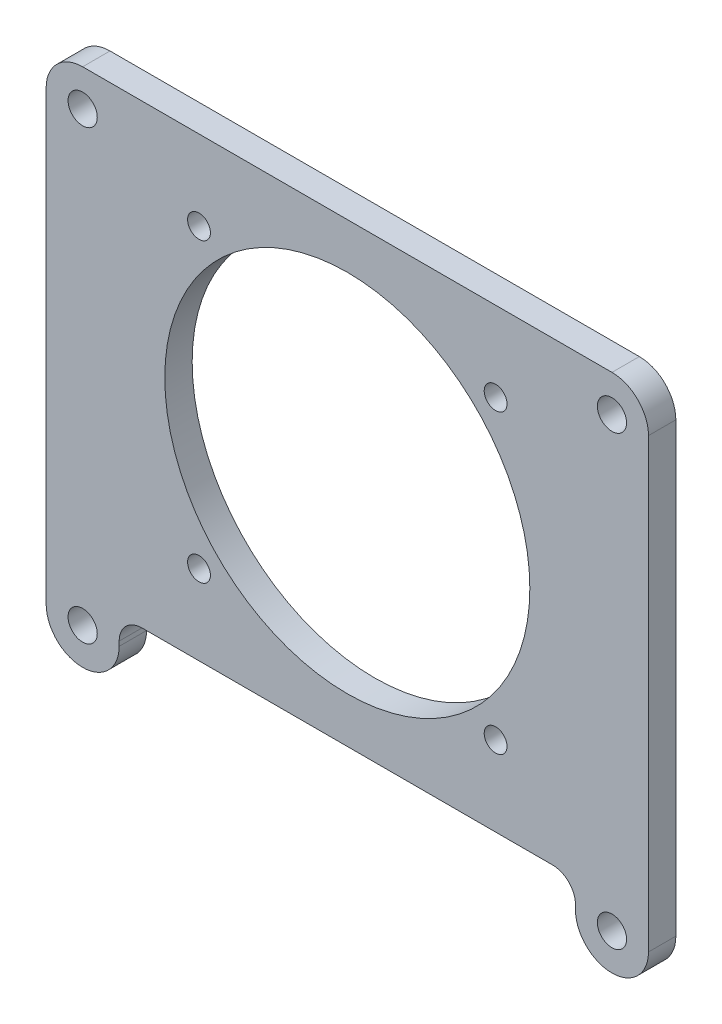
SolidWorks part; units mm, degrees
ref_plane "正面" through (0, 0, 0) normal (0, 0, 1) x (1, 0, 0)
ref_plane "平面" through (0, 0, 0) normal (0, 1, 0) x (1, 0, 0)
ref_plane "右側面" through (0, 0, 0) normal (1, 0, 0) x (0, 0, -1)
sketch "ｽｹｯﾁ1" plane through (0, 0, 0) normal (0, 0, 1) x (1, 0, 0)
  line L0 (22.5, 0) -> (-22.5, 0)
  line L1 (-25, -2.5) -> (-25, -3)
  line L2 (-33, -3) -> (-33, 46)
  line L3 (-29, 50) -> (29, 50)
  line L4 (0, 50) -> (0, 0) construction
  line L5 (-29, 46) -> (-29, -3) construction
  line L6 (33, -3) -> (33, 46)
  line L7 (25, -2.5) -> (25, -3)
  arc A0 (-33, -3) -> (-25, -3) centre (-29, -3) ccw
  arc A1 (-29, 50) -> (-33, 46) centre (-29, 46) ccw
  arc A2 (-25, -2.5) -> (-22.5, 0) centre (-22.5, -2.5) cw
  circle A3 centre (-29, -3) radius 1.6
  circle A4 centre (-29, 46) radius 1.6
  circle A5 centre (29, 46) radius 1.6
  circle A6 centre (29, -3) radius 1.6
  arc A7 (25, -2.5) -> (22.5, 0) centre (22.5, -2.5) ccw
  arc A8 (29, 50) -> (33, 46) centre (29, 46) cw
  arc A9 (33, -3) -> (25, -3) centre (29, -3) cw
  dimension "D1" = 49
  dimension "D3" = 2.5
  dimension "D4" = 3.2
  dimension "D5" = 4
  dimension "D2" = 29
  dimension "D6" = 3
extrude "ﾎﾞｽ - 押し出し1" add sketch "ｽｹｯﾁ1" along normal blind 3
sketch "ｽｹｯﾁ2" plane through (0, 0, 3) normal (0, 0, 1) x (1, 0, 0)
  line L0 (0, 25) -> (0, 0) construction
  line L1 (-16.25, 41.25) -> (16.25, 41.25) construction
  line L2 (-16.25, 41.25) -> (-16.25, 8.75) construction
  line L3 (-16.25, 8.75) -> (16.25, 8.75) construction
  line L4 (16.25, 41.25) -> (16.25, 8.75) construction
  line L5 (-16.25, 41.25) -> (16.25, 8.75) construction
  line L6 (-16.25, 8.75) -> (16.25, 41.25) construction
  circle A0 centre (-16.25, 41.25) radius 1.25
  circle A1 centre (-16.25, 8.75) radius 1.25
  circle A2 centre (16.25, 8.75) radius 1.25
  circle A3 centre (16.25, 41.25) radius 1.25
  circle A4 centre (0, 25) radius 20
  point P0 (0, 25)
  dimension "D1" = 2.5
  dimension "D3" = 40
  dimension "D2" = 32.5
  dimension "D4" = 25
extrude "ｶｯﾄ - 押し出し1" cut sketch "ｽｹｯﾁ2" against normal through all
